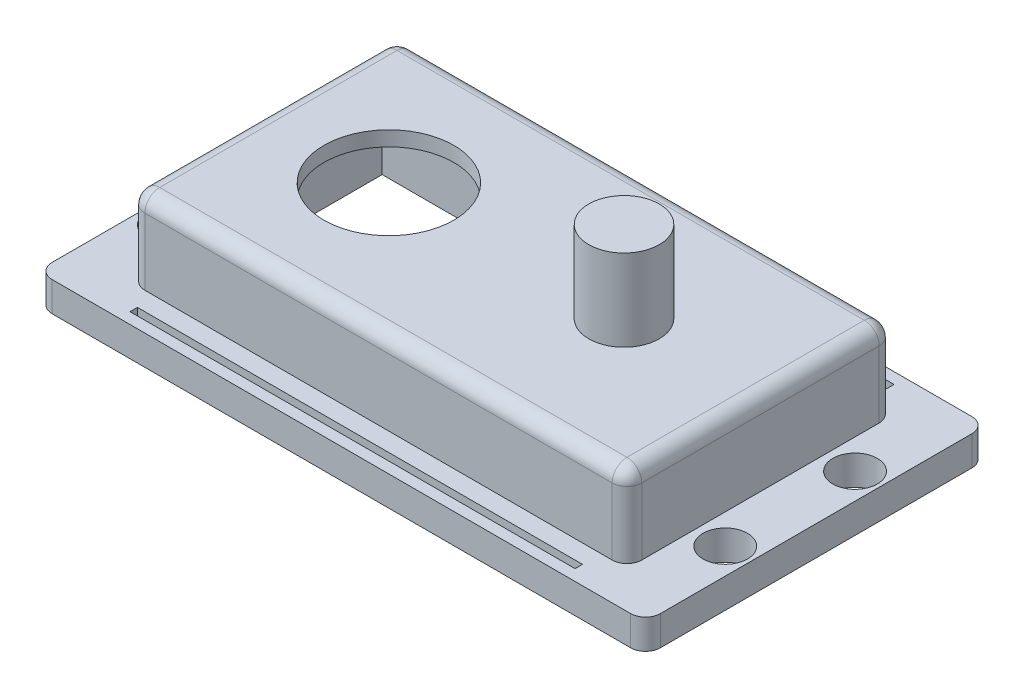
SolidWorks part; units mm, degrees
ref_plane "Plan de face" through (0, 0, 0) normal (0, 0, 1) x (1, 0, 0)
ref_plane "Plan de dessus" through (0, 0, 0) normal (0, 1, 0) x (1, 0, 0)
ref_plane "Plan de droite" through (0, 0, 0) normal (1, 0, 0) x (0, 0, -1)
sketch "Esquisse1" plane through (0, 0, 0) normal (0, 1, 0) x (1, 0, 0)
  line L0 (0, 23) -> (0, -23) construction
  line L1 (41, -23) -> (-41, -23)
  line L2 (41, -23) -> (41, 23)
  line L3 (41, 23) -> (-41, 23)
  line L4 (-41, -23) -> (-41, 23)
  line L5 (41, -23) -> (-41, 23) construction
  line L6 (41, 23) -> (-41, -23) construction
  line L7 (-41, 0) -> (41, 0) construction
  line L8 (30, 21.5) -> (-30, 20.5) construction
  line L9 (30, -20.5) -> (-30, -20.5)
  line L10 (30, -20.5) -> (30, -21.5)
  line L11 (30, -21.5) -> (-30, -21.5)
  line L12 (-30, -20.5) -> (-30, -21.5)
  line L13 (30, -20.5) -> (-30, -21.5) construction
  line L14 (30, -21.5) -> (-30, -20.5) construction
  line L15 (30, 20.5) -> (-30, 21.5) construction
  line L16 (30, 20.5) -> (30, 21.5)
  line L17 (30, 21.5) -> (-30, 21.5)
  line L18 (-30, 20.5) -> (-30, 21.5)
  line L19 (30, 20.5) -> (-30, 20.5)
  circle A0 centre (-37.5, 8.75) radius 3
  circle A4 centre (37.5, 8.75) radius 3
  circle A5 centre (37.5, -8.75) radius 3
  circle A6 centre (-37.5, -8.75) radius 3
  point P0 (0, 0)
  point P8 (0, 0)
  point P9 (0, -21)
  point P18 (0, 21)
  dimension "D3" = 6
  dimension "D1" = 46
  dimension "D2" = 82
  dimension "D4" = 75
  dimension "D5" = 17.5
  dimension "D8" = 37.5
  dimension "D9" = 8.75
  dimension "D10" = 60
  dimension "D11" = 1
  dimension "D12" = 2
  dimension "D6" = 2
  dimension "D7" = 2
extrude "Boss.-Extru.1" add sketch "Esquisse1" along normal blind 15 contours L1 L4 L3 L2 | A6 | A0 | A5 | A4
sketch "Esquisse2" plane through (0, 0, 0) normal (0, 1, 0) x (1, 0, 0)
  line L1 (33, -15.5) -> (-33, -15.5)
  line L2 (33, -15.5) -> (33, 15.5)
  line L3 (33, 15.5) -> (-33, 15.5)
  line L4 (-33, -15.5) -> (-33, 15.5)
  line L5 (33, -15.5) -> (-33, 15.5) construction
  line L6 (33, 15.5) -> (-33, -15.5) construction
  point P0 (0, 0)
  dimension "D1" = 66
  dimension "D2" = 31
extrude "Enlèv. mat.-Extru.1" cut sketch "Esquisse2" along normal blind 13
sketch "Esquisse3" plane through (0, 0, 0) normal (0, 1, 0) x (1, 0, 0)
  line L0 (-41, 0) -> (41, 0) construction
  circle A0 centre (-16.6, 0) radius 8.75
  circle A1 centre (-16.6, 0) radius 3.8
  dimension "D1" = 17.5
  dimension "D3" = 7.6
  dimension "D2" = 16.6
extrude "Enlèv. mat.-Extru.2" cut sketch "Esquisse3" against normal through all from surface contours A0 starting at face at (37.5, 15, 11.75)
sketch "Esquisse4" plane through (0, 0, 0) normal (0, 1, 0) x (1, 0, 0)
  line L0 (-41, 23) -> (-41, -23) construction
  line L1 (-33.5, -23) -> (-41, -23)
  line L2 (-33.5, -18) -> (-33.5, 18)
  line L3 (-33.5, 23) -> (-41, 23)
  line L4 (-41, -23) -> (-41, 23)
  line L5 (-33.5, -23) -> (-41, 23) construction
  line L6 (-33.5, 23) -> (-41, -23) construction
  line L7 (41, 23) -> (-41, 23) construction
  line L8 (-41, -23) -> (41, -23) construction
  line L9 (0, -23) -> (0, 23) construction
  line L10 (33.5, 23) -> (41, -23) construction
  line L11 (33.5, -23) -> (41, 23) construction
  line L12 (33.5, 23) -> (41, 23)
  line L13 (33.5, -23) -> (41, -23)
  line L14 (41, -23) -> (41, 23)
  line L15 (33.5, -18) -> (33.5, 18)
  line L16 (41, 23) -> (-41, 23) construction
  line L17 (33.5, 18) -> (-33.5, 18)
  line L19 (33.5, 23) -> (-33.5, 23)
  line L23 (-33.5, 0) -> (33.5, 0) construction
  line L26 (33.5, -23) -> (-33.5, -23)
  line L27 (33.5, -18) -> (-33.5, -18)
  point P0 (-37.25, 0)
  point P13 (0, 20.5)
  point P26 (0, -20.5)
  dimension "D1" = 7.5
  dimension "D2" = 5
  dimension "D3" = 7.5
  dimension "D4" = 7.5
extrude "Enlèv. mat.-Extru.3" cut sketch "Esquisse4" against normal blind 11 from surface starting at face at (-16.6, 15, 8.75)
sketch "Esquisse5" plane through (0, 0, 0) normal (0, 1, 0) x (1, 0, 0)
  circle A0 centre (15.1, 0) radius 4.75
  dimension "D1" = 9.5
  dimension "D2" = 31.7
extrude "Boss.-Extru.3" add sketch "Esquisse5" along normal blind 11 from surface starting at face at (0, 15, 0)
extrude "Enlèv. mat.-Extru.4" cut sketch "Esquisse1<4>" against normal blind 1 from surface contours L12 L11 L10 L9 | L19 L18 L17 L16 starting at face at (-37.5, 4, 5.75)
sketch "Esquisse1<4>" plane through (0, 0, 0) normal (0, 1, 0) x (1, 0, 0) same geometry as "Esquisse1"
fillet "Congé1" radius 2 4 edges at (33.5, 15, 0) (-33.5, 15, 0) (0, 15, 18) (0, 15, -18)
fillet "Congé2" radius 2 8 edges at (-32.9142, 14.4142, -17.4142) (32.9142, 14.4142, -17.4142) (32.9142, 14.4142, 17.4142) (-32.9142, 14.4142, 17.4142) (-33.5, 8.5, -18) (33.5, 8.5, -18) (33.5, 8.5, 18) (-33.5, 8.5, 18)
fillet "Congé4" radius 2 4 edges at (41, 2, 23) (-41, 2, 23) (-41, 2, -23) (41, 2, -23)
equation "\"D8@Esquisse1\"=\"D4@Esquisse1\"/2"
equation "\"D9@Esquisse1\"=\"D5@Esquisse1\"/2"
equation "\"Module\"= 1.5"
equation "\"Number of teeth\"= 21"
equation "\"Pressure angle\"= 20"
equation "\"D2@Esquisse5\"=(\"Module\"*(2*\"Number of teeth\")/2)+0.2"
